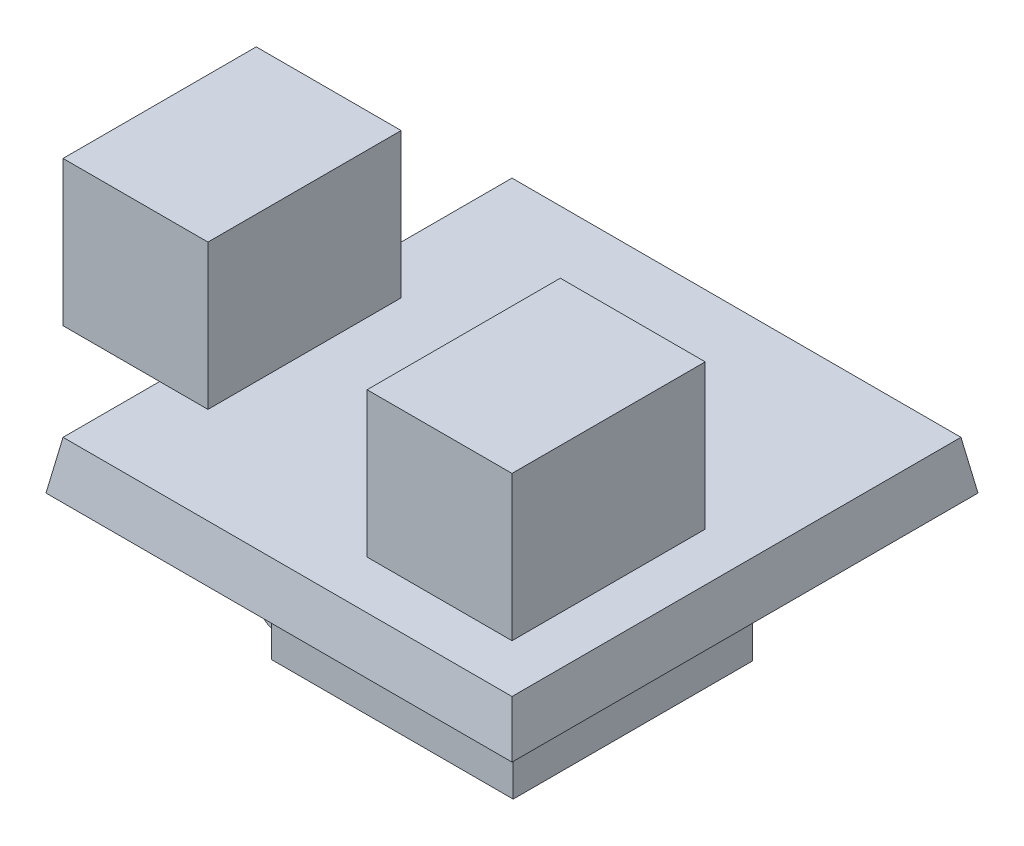
SolidWorks part; units mm, degrees
ref_plane "Front Plane" through (0, 0, 0) normal (0, 0, 1) x (1, 0, 0)
ref_plane "Top Plane" through (0, 0, 0) normal (0, 1, 0) x (1, 0, 0)
ref_plane "Right Plane" through (0, 0, 0) normal (1, 0, 0) x (0, 0, -1)
sketch "Sketch1" plane through (0, 0, 0) normal (0, 1, 0) x (1, 0, 0)
  line L1 (-50, 50) -> (50, 50)
  line L2 (-50, 50) -> (-50, -50)
  line L3 (-50, -50) -> (50, -50)
  line L4 (50, 50) -> (50, -50)
  line L5 (-50, 50) -> (50, -50) construction
  line L6 (-50, -50) -> (50, 50) construction
  point P0 (0, 0)
  dimension "D1" = 100
  dimension "D2" = 100
extrude "Boss-Extrude1" add sketch "Sketch1" along normal blind 20 draft 10
sketch "Sketch2" plane through (0, 20, 0) normal (0, 1, 0) x (1, 0, 0)
  line L1 (-46.4735, -46.4735) -> (-16.4735, -46.4735)
  line L2 (-46.4735, -46.4735) -> (-46.4735, -6.4735)
  line L3 (-46.4735, -6.4735) -> (-16.4735, -6.4735)
  line L4 (-16.4735, -46.4735) -> (-16.4735, -6.4735)
  dimension "D1" = 40
  dimension "D2" = 30
extrude "Boss-Extrude2" add sketch "Sketch2" along normal blind 20 and the other way blind 10 from offset 30 separate body contours L2 L1 L4 L3
sketch "Sketch3" plane through (0, 20, 0) normal (0, 1, 0) x (1, 0, 0)
  line L1 (46.4735, -46.4735) -> (16.4735, -46.4735)
  line L2 (46.4735, -46.4735) -> (46.4735, -6.4735)
  line L3 (46.4735, -6.4735) -> (16.4735, -6.4735)
  line L4 (16.4735, -46.4735) -> (16.4735, -6.4735)
  dimension "D1" = 40
  dimension "D2" = 30
extrude "Boss-Extrude3" add sketch "Sketch3" along normal blind 30 from offset 10 contours L2 L1 L4 L3
sketch "Sketch5" plane through (0, 20, 0) normal (0, 1, 0) x (1, 0, 0)
  circle A0 centre (0, 0) radius 15
  dimension "D1" = 30
extrude "Cut-Extrude1" cut sketch "Sketch5" against normal blind 30
mirror "Mirror3" about plane through (0, 0, 0) normal (0, 1, 0) of "Boss-Extrude1"
sketch "Sketch7" plane through (0, -20, 0) normal (0, -1, 0) x (1, 0, 0)
  line L1 (-25, 24.7516) -> (25, 24.7516)
  line L2 (-25, 24.7516) -> (-25, -24.7516)
  line L3 (-25, -24.7516) -> (25, -24.7516)
  line L4 (25, 24.7516) -> (25, -24.7516)
  line L5 (-25, 24.7516) -> (25, -24.7516) construction
  line L6 (-25, -24.7516) -> (25, 24.7516) construction
  circle A0 centre (-25, 0) radius 20
  point P0 (0, 0)
  dimension "D3" = 40
  dimension "D1" = 50
  dimension "D2" = 49.5032
extrude "Cut-Extrude2" cut sketch "Sketch7" against normal blind 30 flip side to cut contours A0 L2 L3 L4 L1 | L2 A0 | L2 A0 region at (5.6175, -20, 0) region at (-16.5117, -20, 0) region at (-33.4883, -20, 0)
